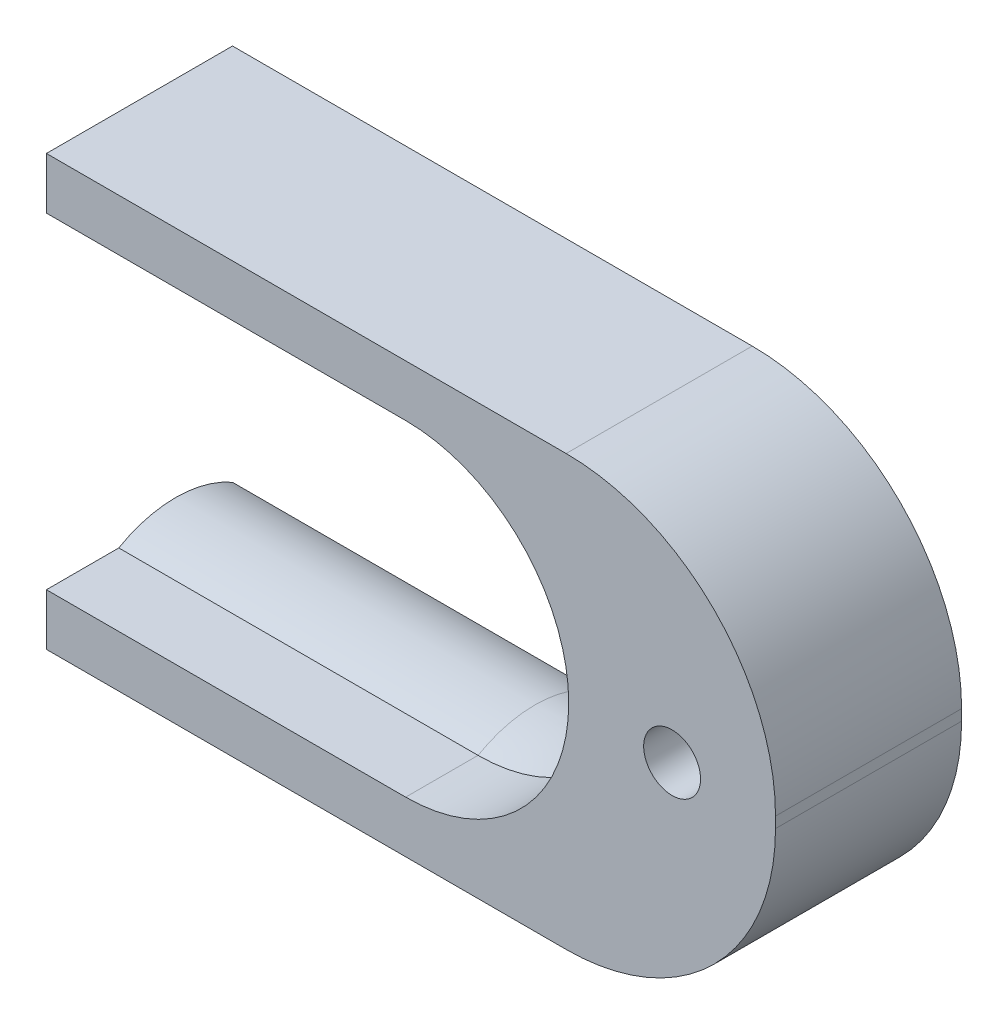
SolidWorks part; units mm, degrees
ref_plane "Top" through (0, 0, 0) normal (0, 0, 1) x (1, 0, 0)
ref_plane "Front" through (0, 0, 0) normal (0, 1, 0) x (1, 0, 0)
ref_plane "Right" through (0, 0, 0) normal (1, 0, 0) x (0, 0, -1)
sketch "Sketch1" plane through (0, 0, 0) normal (0, 0, 1) x (1, 0, 0)
  line L0 (0, 0) -> (34.75, 0)
  line L1 (34.75, 28.6) -> (0, 28.6)
  arc A0 (34.75, 0) -> (34.75, 28.6) centre (34.75, 14.3) ccw
  dimension "D1" = 28.6
  dimension "D2" = 34.75
sketch "Sketch2" plane through (0, 0, 0) normal (1, 0, 0) x (0, 0, -1)
  line L4 (-5.5, -1.4737) -> (5.5, -1.4737)
  arc A2 (-5.5, -1.4737) -> (5.5, -1.4737) centre (0, -11) cw
  dimension "D1" = 11
  dimension "D2" = 11
  dimension "D3" = 5.5
sweep "Sweep1" add profiles "Sketch2" path "Sketch1"
sketch "Sketch3" plane through (0, 0, 0) normal (0, 0, 1) x (1, 0, 0)
  line L0 (0, 30.0737) -> (0, 35.0737)
  line L1 (0, 35.0737) -> (50.2737, 35.0737)
  line L2 (70.5237, 14.8237) -> (70.5237, 13.7763)
  line L3 (50.2737, -6.4737) -> (0, -6.4737)
  line L4 (0, -6.4737) -> (0, -1.4737)
  line L5 (0, 30.0737) -> (34.75, 30.0737)
  line L6 (0, -1.4737) -> (34.75, -1.4737)
  line L7 (0, -1.4737) -> (34.75, -1.4737) construction
  arc A0 (34.75, -1.4737) -> (34.75, 30.0737) centre (34.75, 14.3) ccw construction
  arc A1 (34.75, 30.0737) -> (34.75, -1.4737) centre (34.75, 14.3) cw
  arc A2 (50.2737, -6.4737) -> (70.5237, 13.7763) centre (50.2737, 13.7763) ccw
  arc A3 (70.5237, 14.8237) -> (50.2737, 35.0737) centre (50.2737, 14.8237) ccw
  circle A4 centre (60.5237, 14.3) radius 2.75
  point P18 (50.5237, 14.3)
  point P25 (0, 0)
  dimension "D3" = 20.25
  dimension "D4" = 5.5
  dimension "D5" = 10
  dimension "D1" = 5
  dimension "D2" = 20
extrude "Boss-Extrude1" add sketch "Sketch3" along normal blind 12.5 and the other way blind 5.5
hole_wizard "CBORE for M5 Hex Socket Head Cap Screw2" positions "Sketch8" profile "Sketch9" counterbore size "M5" standard "DIN" end condition through all
sketch "Sketch8" plane through (0, 0, -5.5) normal (0, 0, -1) x (-1, 0, 0)
  point P0 (-60.5237, 14.3)
sketch "Sketch9" plane through (60.5237, 14.3, -5.5) normal (1, 0, 0) x (0, 1, 0)
  line L0 (0, 0) -> (0, 18)
  line L1 (0, 18) -> (2.75, 18)
  line L3 (2.75, 18) -> (2.75, 5.4)
  line L4 (2.75, 5.4) -> (5, 5.4)
  line L5 (5, 5.4) -> (5, 0)
  line L7 (5, 0) -> (0, 0)
  line L11 (0, -6.35) -> (0, 107.95) construction
  dimension "Thru Hole Dia." = 5.5
  dimension "Thru Hole Depth" = 18
  dimension "C'Bore Dia." = 10
  dimension "C'Bore Depth" = 5.4
